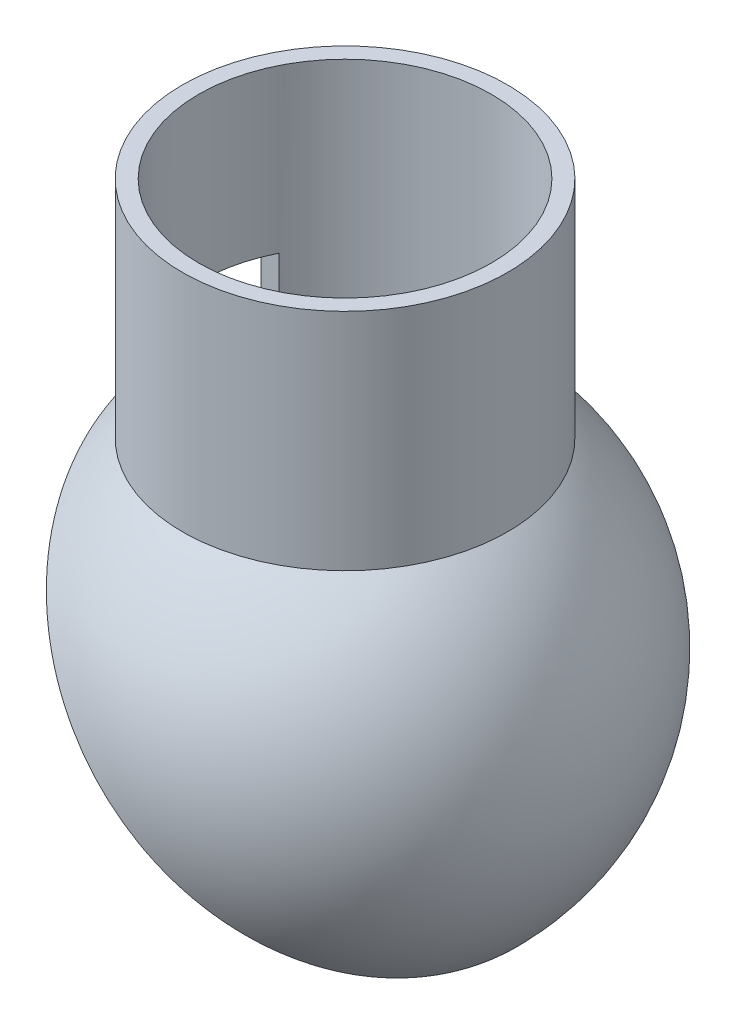
SolidWorks part; units mm, degrees
ref_plane "前视基准面" through (0, 0, 0) normal (0, 0, 1) x (1, 0, 0)
ref_plane "上视基准面" through (0, 0, 0) normal (0, 1, 0) x (1, 0, 0)
ref_plane "右视基准面" through (0, 0, 0) normal (1, 0, 0) x (0, 0, -1)
sketch "草图1" plane through (0, 0, 0) normal (0, 0, 1) x (1, 0, 0)
  line L4 (0, 25) -> (-10, 25)
  line L7 (-10, 25) -> (-10, 11.1803)
  line L9 (0, 25) -> (0, -15)
  arc A2 (-10, 11.1803) -> (0, -15) centre (0, 0) ccw
revolve "旋转2" add sketch "草图1" angle 360 about L9 region at (-6.1037, 4.6552, 0)
sketch "草图4" plane through (0, 0, 0) normal (0, 0, 1) x (1, 0, 0)
  line L0 (0, 0) -> (-10.6066, 10.6066)
  line L1 (0, 0) -> (10.6066, -10.6066)
  arc A0 (-10, 11.1803) -> (10, 11.1803) centre (0, 0) ccw construction
  arc A1 (10.6066, -10.6066) -> (-10.6066, 10.6066) centre (0, 0) cw
extrude "切除-拉伸1" cut sketch "草图4" against normal through all and the other way through all contours A1 L1 L0 region at (-4.5016, -4.5016, 0)
ref_plane "基准面4" through (0, 25, 0) normal (0, 1, 0) x (1, 0, 0)
sketch "草图5" plane through (0, 25, 0) normal (0, 1, 0) x (1, 0, 0)
  circle A0 centre (0, 0) radius 9
extrude "切除-拉伸2" cut sketch "草图5" against normal blind 15
sketch "草图6" plane through (0, 0, 0) normal (1, 0, 0) x (0, 0, -1)
  line L1 (0, 12) -> (4, 12)
  line L2 (0, 12) -> (-4, 12)
  line L3 (4, 12) -> (4, 15)
  line L4 (4, 15) -> (-4, 15)
  line L5 (-4, 15) -> (-4, 12)
extrude "切除-拉伸3" cut sketch "草图6" against normal blind 14
